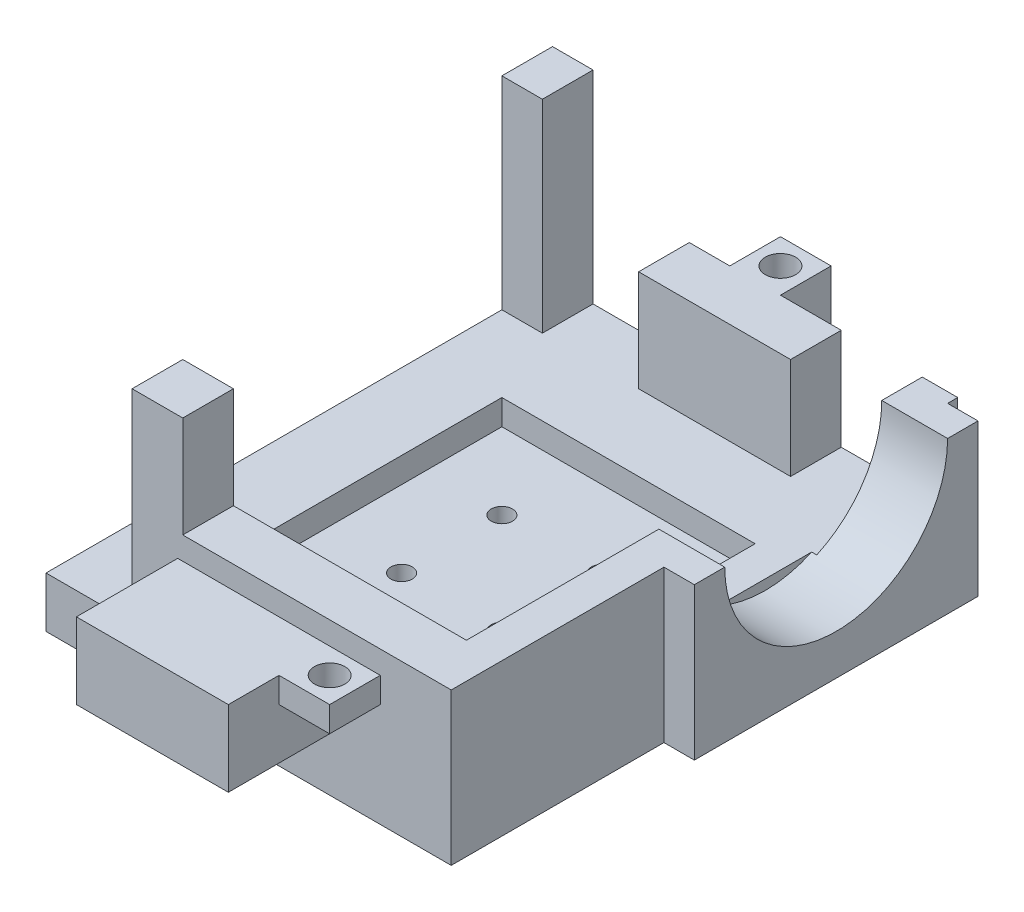
SolidWorks part; units mm, degrees
ref_plane "Front Plane" through (0, 0, 0) normal (0, 0, 1) x (1, 0, 0)
ref_plane "Top Plane" through (0, 0, 0) normal (0, 1, 0) x (1, 0, 0)
ref_plane "Right Plane" through (0, 0, 0) normal (1, 0, 0) x (0, 0, -1)
sketch "Sketch1" plane through (0, 0, 0) normal (0, 1, 0) x (1, 0, 0)
  line L1 (-20, 25) -> (20, 25)
  line L2 (-20, 25) -> (-20, -25)
  line L3 (-20, -25) -> (20, -25)
  line L4 (20, 25) -> (20, -25)
  point P5 (-20, 0)
  point P6 (0, 25)
  dimension "D1" = 40
  dimension "D2" = 50
extrude "Boss-Extrude1" add sketch "Sketch1" along normal blind 5
sketch "Sketch4" plane through (0, 5, 0) normal (0, 1, 0) x (1, 0, 0)
  line L0 (-20, -25) -> (20, -25) construction
  line L1 (20, 25) -> (16.5, 25)
  line L2 (20, 25) -> (20, -25)
  line L4 (16.5, 25) -> (16.5, -20)
  line L5 (20, 25) -> (-20, 25) construction
  line L8 (16.5, -20) -> (-6.5, -20)
  line L9 (-6.5, -25) -> (-6.5, -20)
  line L10 (-20, 25) -> (-16, 25)
  line L11 (-20, 25) -> (-20, 20)
  line L12 (-20, 20) -> (-16, 20)
  line L13 (-16, 25) -> (-16, 20)
  line L14 (-6.5, 25) -> (8.5, 25)
  line L15 (-6.5, 25) -> (-6.5, 20)
  line L16 (-6.5, 20) -> (8.5, 20)
  line L17 (8.5, 25) -> (8.5, 20)
  line L18 (-6.5, -25) -> (20, -25)
  line L19 (-11.5, 25) -> (-11.5, 20) construction
  line L20 (-11.5, 20) -> (-6.5, 20) construction
  line L21 (-16, -25) -> (-16, -20) construction
  line L22 (-16, -20) -> (-20, -20) construction
  line L23 (-20, 25) -> (-20, -25) construction
  line L25 (-6.5, -20) -> (-11.5, -20)
  line L26 (-6.5, -20) -> (-6.5, -25)
  line L27 (-6.5, -25) -> (-11.5, -25)
  line L28 (-11.5, -20) -> (-11.5, -25)
  line M19 (-20, 25) -> (-20, -25)
  line M20 (-20, -25) -> (20, -25)
  line M21 (20, -25) -> (20, 25)
  line M22 (20, 25) -> (-20, 25)
  dimension "D1" = 3.5
  dimension "D2" = 5
  dimension "D3" = 4
  dimension "D4" = 15
  dimension "D5" = 5
  dimension "D6" = 8
extrude "Boss-Extrude4" add sketch "Sketch4" along normal blind 20 contours L25 L28 L9 M20 | L13 L12 M22 M19 region at (-9, 5, 22.5) region at (-18, 5, -22.5)
extrude "Boss-Extrude5" add sketch "Sketch4<4>" along normal blind 10 contours L9 L4 L8 M20 M21 M22 | L17 L15 L16 M22 region at (19.4341, 5, 0) region at (1, 5, -22.5)
sketch "Sketch4<4>" plane through (0, 5, 0) normal (0, 1, 0) x (1, 0, 0) same geometry as "Sketch4"
sketch "Sketch7" plane through (20, 0, 0) normal (1, 0, 0) x (0, 0, -1)
  line L0 (-25, 15) -> (25, 15) construction
  line L1 (-1, 15) -> (21, 15)
  line L2 (25, 15) -> (25, 0) construction
  arc A0 (-1, 15) -> (21, 15) centre (10, 15) ccw
  dimension "D1" = 22
  dimension "D2" = 15
extrude "Cut-Extrude2" cut sketch "Sketch7" against normal blind 4
sketch "Sketch8" plane through (20, 0, 0) normal (1, 0, 0) x (0, 0, -1)
  line L0 (-1, 15) -> (-4, 15)
  line L1 (-25, 15) -> (-1, 15) construction
  line L2 (-4, 15) -> (-4, 0)
  line L3 (-25, 0) -> (25, 0) construction
  line L4 (-4, 0) -> (24, 0)
  line L5 (24, 0) -> (24, 15)
  line L6 (21, 15) -> (25, 15) construction
  line L7 (24, 15) -> (21, 15)
  line L8 (25, 15) -> (25, 0) construction
  arc A0 (-1, 15) -> (21, 15) centre (10, 15) ccw
  dimension "D2" = 22
  dimension "D1" = 3
  dimension "D3" = 1
extrude "Boss-Extrude7" add sketch "Sketch8" along normal blind 3
sketch "Sketch11" plane through (0, 0, -25) normal (0, 0, -1) x (-1, 0, 0)
  line L0 (-8.5, 15) -> (6.5, 15) construction
  line L1 (2.5, 15) -> (-2.5, 15)
  line L2 (2.5, 15) -> (2.5, 10)
  line L3 (2.5, 10) -> (-2.5, 10)
  line L4 (-2.5, 15) -> (-2.5, 10)
  line L6 (-20, 0) -> (20, 0) construction
  point P8 (0, 0)
  point P9 (0, 10)
  dimension "D1" = 5
  dimension "D2" = 5
extrude "Boss-Extrude8" add sketch "Sketch11" along normal blind 5
sketch "Sketch12" plane through (0, 10, 0) normal (0, -1, 0) x (1, 0, 0)
  line L0 (2.5, -30) -> (-2.5, -30) construction
  line L1 (2.5, -30) -> (2.5, -25) construction
  circle A0 centre (0, -27.5) radius 1.5
  point P6 (0, -30)
  point P10 (2.5, -27.5)
  dimension "D1" = 3
extrude "Cut-Extrude6" cut sketch "Sketch12" against normal blind 5
sketch "Sketch15" plane through (0, 0, 25) normal (0, 0, 1) x (1, 0, 0)
  line L0 (-20, 0) -> (20, 0) construction
  line L2 (13, 12.75) -> (13, 10.25)
  line L3 (13, 10.25) -> (8, 10.25)
  line L4 (8, 10.25) -> (8, 5.25)
  line L5 (8, 5.25) -> (-7, 5.25)
  line L6 (-7, 5.25) -> (-7, 12.75)
  line L7 (-7, 12.75) -> (13, 12.75)
  line L9 (8, 10.25) -> (8, 12.75)
  point P3 (0, 0)
  dimension "D1" = 5
  dimension "D2" = 2.5
  dimension "D3" = 7
  dimension "D4" = 7.5
  dimension "D5" = 8
  dimension "D6" = 5.25
extrude "Boss-Extrude11" add sketch "Sketch15" along normal blind 5 contours L9 L3 L2 L7 region at (10.5, 11.5, 25)
extrude "Boss-Extrude12" add sketch "Sketch15<3>" along normal blind 10 contours L4 L9 L7 L6 L5 region at (0.5, 9, 25)
sketch "Sketch15<3>" plane through (0, 0, 25) normal (0, 0, 1) x (1, 0, 0) same geometry as "Sketch15"
sketch "Sketch16" plane through (0, 10.25, 0) normal (0, -1, 0) x (1, 0, 0)
  line L0 (13, 30) -> (13, 25) construction
  line L1 (13, 30) -> (8, 30) construction
  circle A0 centre (10.5, 27.5) radius 1.5
  point P4 (13, 27.5)
  point P7 (10.5, 30)
  dimension "D1" = 3
extrude "Cut-Extrude8" cut sketch "Sketch16" against normal blind 2.5
sketch "Sketch18" plane through (0, 0, 0) normal (0, -1, 0) x (1, 0, 0)
  line L0 (20, -25) -> (-20, -25) construction
  line L1 (0, -25) -> (0, 25) construction
  line L2 (-20, 25) -> (20, 25) construction
  line L3 (-20, -25) -> (-20, 25) construction
  line L4 (-20, 0) -> (23, 0) construction
  line L5 (23, 4) -> (23, -24) construction
  line L6 (-4.9497, 4.9497) -> (-4.9497, -4.9497) construction
  line L7 (-4.9497, -4.9497) -> (4.9497, -4.9497) construction
  line L8 (4.9497, -4.9497) -> (4.9497, 4.9497) construction
  line L9 (4.9497, 4.9497) -> (-4.9497, 4.9497) construction
  circle A0 centre (-4.9497, 4.9497) radius 1.05
  circle A1 centre (4.9497, 4.9497) radius 1.05
  circle A2 centre (4.9497, -4.9497) radius 1.05
  circle A3 centre (-4.9497, -4.9497) radius 1.05
  point P17 (0, -4.9497)
  point P18 (-4.9497, 0)
  dimension "D3" = 2.1
  dimension "D1" = 14
extrude "Cut-Extrude9" cut sketch "Sketch18" against normal blind 5
sketch "Sketch19" plane through (0, 5, 0) normal (0, 1, 0) x (1, 0, 0)
  line L1 (-12.5, 12.5) -> (12.5, 12.5)
  line L2 (-12.5, 12.5) -> (-12.5, -12.5)
  line L3 (-12.5, -12.5) -> (12.5, -12.5)
  line L4 (12.5, 12.5) -> (12.5, -12.5)
  point P6 (0, 12.5)
  point P7 (12.5, 0)
  dimension "D1" = 25
extrude "Cut-Extrude10" cut sketch "Sketch19" against normal blind 2.5
